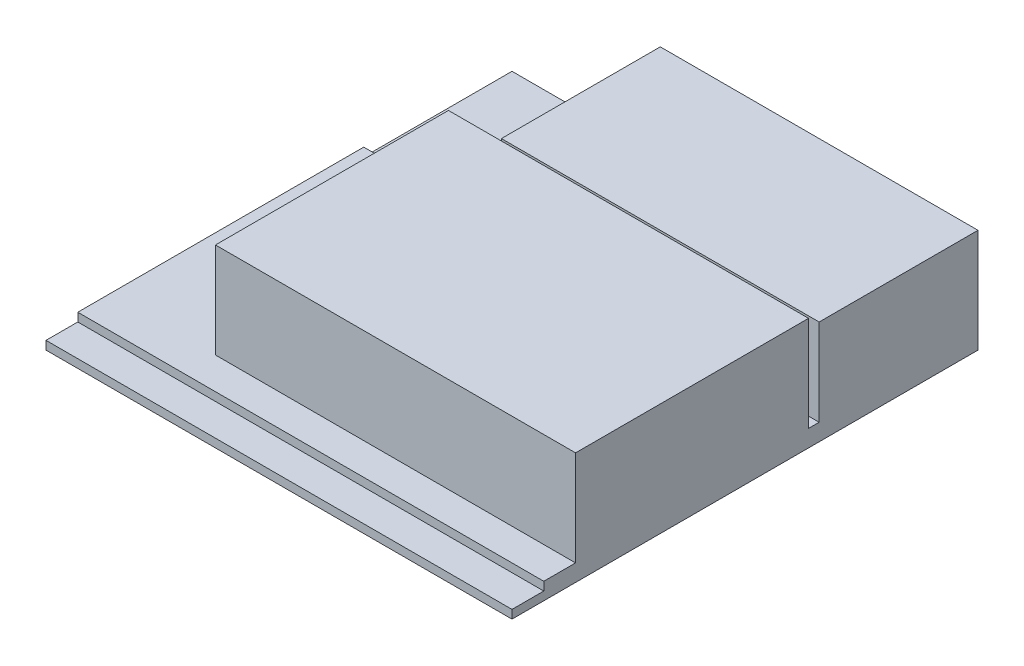
SolidWorks part; units mm, degrees
ref_plane "Front Plane" through (0, 0, 0) normal (0, 0, 1) x (1, 0, 0)
ref_plane "Top Plane" through (0, 0, 0) normal (0, 1, 0) x (1, 0, 0)
ref_plane "Right Plane" through (0, 0, 0) normal (1, 0, 0) x (0, 0, -1)
sketch "Sketch1" plane through (0, 0, 0) normal (0, 1, 0) x (1, 0, 0)
  line L1 (-128.3019, 71.5094) -> (91.6981, 71.5094)
  line L2 (-128.3019, 71.5094) -> (-128.3019, -148.4906)
  line L3 (-128.3019, -148.4906) -> (91.6981, -148.4906)
  line L4 (91.6981, 71.5094) -> (91.6981, -148.4906)
  dimension "D1" = 220
  dimension "D2" = 220
extrude "Boss-Extrude1" add sketch "Sketch1" along normal blind 4
sketch "Sketch2" plane through (0, 4, 0) normal (0, 1, 0) x (1, 0, 0)
  line L0 (-128.3019, -133.4906) -> (91.6981, -133.4906)
  line L1 (-128.3019, 71.5094) -> (-128.3019, -148.4906) construction
  line L2 (91.6981, -148.4906) -> (91.6981, 71.5094) construction
  line L3 (91.6981, -133.4906) -> (91.6981, 1.5094)
  line L4 (91.6981, 1.5094) -> (-128.3019, 1.5094)
  line L5 (-128.3019, 1.5094) -> (-128.3019, -133.4906)
  line L6 (-128.3019, -148.4906) -> (91.6981, -148.4906) construction
  dimension "D1" = 15
  dimension "D2" = 150
extrude "Boss-Extrude2" add sketch "Sketch2" along normal blind 4
sketch "Sketch3" plane through (0, 4, 0) normal (0, 1, 0) x (1, 0, 0)
  line L0 (91.6981, 1.5094) -> (91.6981, 71.5094) construction
  line L1 (-58.3019, 71.5094) -> (91.6981, 71.5094)
  line L2 (-58.3019, 71.5094) -> (-58.3019, -3.4906)
  line L3 (-58.3019, -3.4906) -> (91.6981, -3.4906)
  line L4 (91.6981, 71.5094) -> (91.6981, -3.4906)
  line L5 (91.6981, 71.5094) -> (-128.3019, 71.5094) construction
  dimension "D1" = 150
  dimension "D2" = 75
extrude "Boss-Extrude3" add sketch "Sketch3" along normal blind 45
sketch "Sketch4" plane through (0, 8, 0) normal (0, 1, 0) x (1, 0, 0)
  line L0 (91.6981, -133.4906) -> (91.6981, -3.4906) construction
  line L1 (-78.3019, -8.4906) -> (91.6981, -8.4906)
  line L2 (-78.3019, -8.4906) -> (-78.3019, -118.4906)
  line L3 (-78.3019, -118.4906) -> (91.6981, -118.4906)
  line L4 (91.6981, -8.4906) -> (91.6981, -118.4906)
  line L5 (-128.3019, -148.4906) -> (91.6981, -148.4906) construction
  dimension "D1" = 170
  dimension "D2" = 140
  dimension "D3" = 110
extrude "Boss-Extrude4" add sketch "Sketch4" along normal blind 45
